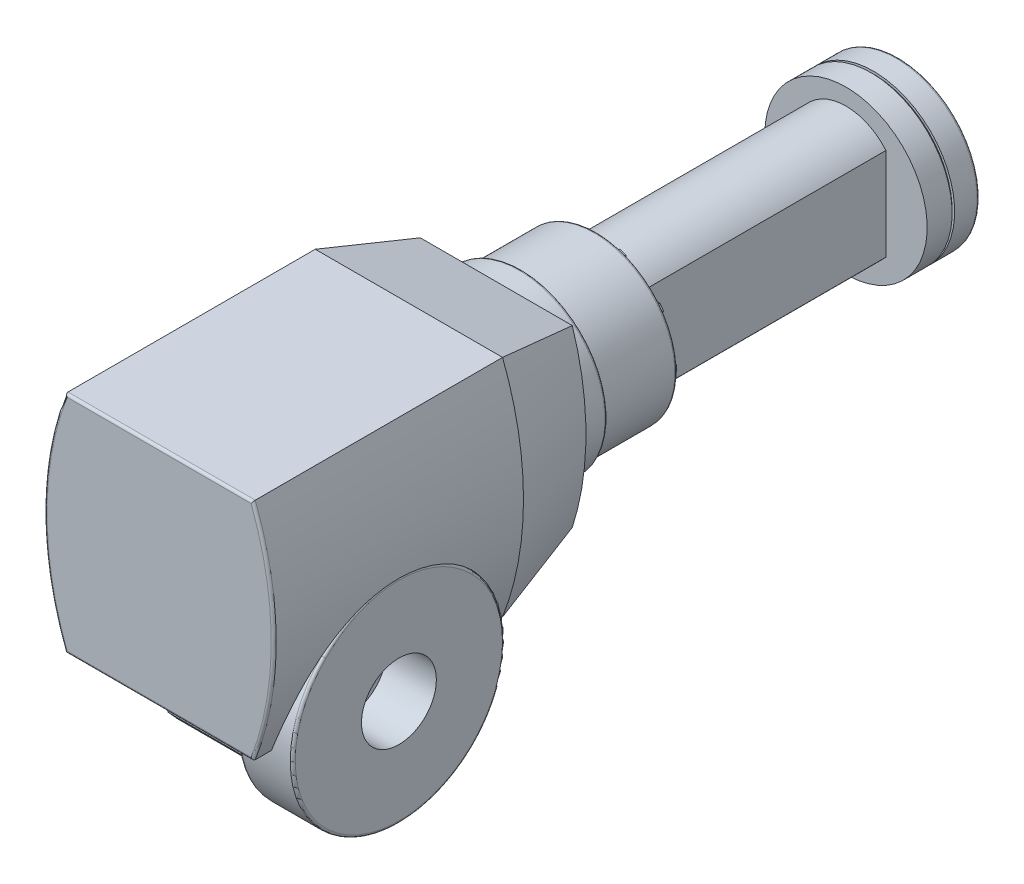
SolidWorks part; units mm, degrees
ref_plane "Front Plane" through (0, 0, 0) normal (0, 0, 1) x (1, 0, 0)
ref_plane "Top Plane" through (0, 0, 0) normal (0, 1, 0) x (1, 0, 0)
ref_plane "Right Plane" through (0, 0, 0) normal (1, 0, 0) x (0, 0, -1)
sketch "Sketch1" plane through (0, 0, 0) normal (0, 0, 1) x (1, 0, 0)
  line L0 (0, -45) -> (0, 45) construction
  line L2 (-37.5, -45) -> (37.5, -45)
  line L3 (-37.5, 45) -> (37.5, 45)
  arc A0 (-37.5, -45) -> (-37.5, 45) centre (79.119, 0) cw
  arc A1 (37.5, -45) -> (37.5, 45) centre (-79.119, 0) ccw
  point P4 (0, 0)
  point P8 (0, 0)
  point P11 (0, -45)
  point P14 (0, 45)
  dimension "D3" = 125
  dimension "D1" = 90
  dimension "D2" = 75
extrude "Boss-Extrude1" add sketch "Sketch1" along normal blind 100
sketch "Sketch2" plane through (0, 0, 0) normal (0, 0, -1) x (-1, 0, 0)
  line L2 (-37.5, -45) -> (37.5, -45)
  line L3 (37.5, 45) -> (-37.5, 45)
  line L4 (-37.5, -45) -> (37.5, -45)
  line L5 (37.5, 45) -> (-37.5, 45)
  arc A2 (-37.5, 45) -> (-37.5, -45) centre (79.119, 0) ccw
  arc A3 (37.5, -45) -> (37.5, 45) centre (-79.119, 0) ccw
  arc A4 (-37.5, 45) -> (-37.5, -45) centre (79.119, 0) ccw
  arc A5 (37.5, -45) -> (37.5, 45) centre (-79.119, 0) ccw
  dimension "D1" = 0
ref_plane "Plane1" through (0, 0, -35) normal (0, 0, -1) x (-1, 0, 0)
sketch "Sketch3" plane through (0, 0, -35) normal (0, 0, -1) x (-1, 0, 0)
  line L4 (-30.4255, -35) -> (30.4255, -35)
  line L5 (30.4255, 35) -> (-30.4255, 35)
  line L6 (-30.4255, -35) -> (30.4255, -35)
  line L7 (30.4255, 35) -> (-30.4255, 35)
  arc A4 (-30.4255, 35) -> (-30.4255, -35) centre (79.119, 0) ccw
  arc A5 (30.4255, -35) -> (30.4255, 35) centre (-79.119, 0) ccw
  arc A6 (-30.4255, 35) -> (-30.4255, -35) centre (79.119, 0) ccw
  arc A7 (30.4255, -35) -> (30.4255, 35) centre (-79.119, 0) ccw
  dimension "D1" = 10
loft "Loft1" add profiles "Sketch3", "Sketch2"
sketch "Sketch4" plane through (0, 0, -35) normal (0, 0, -1) x (-1, 0, 0)
  circle A0 centre (0, 0) radius 34.5
  dimension "D1" = 69
extrude "Boss-Extrude2" add sketch "Sketch4" along normal blind 10
sketch "Sketch5" plane through (0, 0, -45) normal (0, 0, -1) x (-1, 0, 0)
  circle A2 centre (0, 0) radius 32.5
  circle A3 centre (0, 0) radius 32.5
  dimension "D1" = 2
extrude "Boss-Extrude3" add sketch "Sketch5" along normal blind 30
sketch "Sketch6" plane through (0, 0, -75) normal (0, 0, -1) x (-1, 0, 0)
  line L0 (0, 0) -> (29, 0) construction
  line L1 (27.8349, 0.6726) -> (27.8349, -0.6726)
  line L2 (29, -2.5) -> (31.1651, -1.25)
  line L3 (31.1651, -1.25) -> (31.1651, 1.25)
  line L4 (31.1651, 1.25) -> (29, 2.5)
  line L5 (29, 2.5) -> (26.8349, 1.25)
  line L6 (26.8349, 1.25) -> (26.8349, -1.25)
  line L7 (26.8349, -1.25) -> (29, -2.5)
  line L8 (27.8349, -0.6726) -> (29, -1.3453)
  line L9 (29, -1.3453) -> (30.1651, -0.6726)
  line L10 (30.1651, -0.6726) -> (30.1651, 0.6726)
  line L11 (30.1651, 0.6726) -> (29, 1.3453)
  line L12 (29, 1.3453) -> (27.8349, 0.6726)
  circle A0 centre (29, 0) radius 2.1651 construction
  dimension "D1" = 29
  dimension "D2" = 5
  dimension "D3" = 1
extrude "Boss-Extrude4" add sketch "Sketch6" along normal blind 1
pattern_circular "CirPattern1" count 10 over 360 about axis through (0, 0, 0) along (0, 0, 1) of "Boss-Extrude4"
sketch "Sketch7" plane through (0, 0, -75) normal (0, 0, -1) x (-1, 0, 0)
  line L0 (0, -18.5) -> (0, 18.5) construction
  line L1 (0, 0) -> (16, 0) construction
  line L2 (16, -18.5) -> (16, 18.5)
  line L3 (-16, -18.5) -> (-16, 18.5)
  arc A0 (-16, 18.5) -> (16, 18.5) centre (0, 4.8985) cw
  arc A1 (-16, -18.5) -> (16, -18.5) centre (0, -4.8985) ccw
  point P4 (0, 0)
  point P10 (16, 0)
  dimension "D3" = 21
  dimension "D1" = 37
  dimension "D2" = 16
extrude "Boss-Extrude5" add sketch "Sketch7" along normal blind 100
sketch "Sketch8" plane through (0, 0, -175) normal (0, 0, -1) x (-1, 0, 0)
  circle A0 centre (0, 0) radius 32.5 construction
  circle A1 centre (0, 0) radius 32.5
extrude "Boss-Extrude6" add sketch "Sketch8" along normal blind 10
sketch "Sketch9" plane through (0, 0, -185) normal (0, 0, -1) x (-1, 0, 0)
  circle A2 centre (0, 0) radius 31.5
  circle A3 centre (0, 0) radius 31.5
  dimension "D1" = 1
extrude "Boss-Extrude7" add sketch "Sketch9" along normal blind 1
sketch "Sketch10" plane through (0, 0, -186) normal (0, 0, -1) x (-1, 0, 0)
  circle A0 centre (0, 0) radius 32.5 construction
  circle A3 centre (0, 0) radius 32.5
extrude "Boss-Extrude8" add sketch "Sketch10" along normal blind 10 separate body
sketch "Sketch11" plane through (0, 0, -186) normal (0, 0, -1) x (-1, 0, 0)
  circle A1 centre (0, 0) radius 31.5
  circle A2 centre (0, 0) radius 31.5
  dimension "D1" = 0
ref_plane "Plane2" through (35, 0, 0) normal (1, 0, 0) x (0, 0, -1)
sketch "Sketch13" plane through (35, 0, 0) normal (1, 0, 0) x (0, 0, -1)
  line L0 (-100, -45) -> (0, -45) construction
  circle A0 centre (-50, -45) radius 42.5
  dimension "D1" = 85
extrude "Boss-Extrude9" add sketch "Sketch13" along normal mid plane 22 separate body
sketch "Sketch14" plane through (24, 0, 0) normal (-1, 0, 0) x (0, 0, 1)
  line L0 (50, -45) -> (50, -75) construction
  line L1 (100, -45) -> (0, -45) construction
  line L2 (30, -45) -> (30, -75)
  line L3 (70, -45) -> (70, -75)
  line L4 (30, -45) -> (70, -45)
  arc A0 (30, -75) -> (70, -75) centre (50, -60.3358) ccw
  dimension "D4" = 24.8
  dimension "D1" = 30
  dimension "D2" = 20
  dimension "D3" = 20
extrude "Boss-Extrude10" add sketch "Sketch14" along normal blind 35
ref_plane "Plane3" through (0, 0, 50) normal (0, 0, 1) x (1, 0, 0)
sketch "Sketch15" plane through (0, 0, 50) normal (0, 0, 1) x (1, 0, 0)
  line L0 (-11, -45) -> (-11, -90)
  line L1 (-11, -45) -> (-36, -45)
  line L2 (-37.5, -45) -> (37.5, -45) construction
  arc A0 (-36, -45) -> (-11, -90) centre (18.9889, -43.8951) ccw
  dimension "D3" = 55
  dimension "D1" = 25
  dimension "D2" = 45
extrude "Boss-Extrude11" add sketch "Sketch15" against normal mid plane 40
sketch "Sketch16" plane through (-11, 0, 0) normal (1, 0, 0) x (0, 0, -1)
  line L3 (-70, -75) -> (-70, -90)
  line L4 (-70, -90) -> (-30, -90)
  line L5 (-30, -90) -> (-30, -75)
  line L6 (-70, -75) -> (-70, -90)
  line L7 (-70, -90) -> (-30, -90)
  line L8 (-30, -90) -> (-30, -75)
  arc A1 (-70, -75) -> (-30, -75) centre (-50, -60.3358) ccw
  arc A2 (-70, -75) -> (-30, -75) centre (-50, -60.3358) ccw
  dimension "D1" = 0
extrude "Cut-Extrude1" cut sketch "Sketch16" against normal blind 40
fillet "Fillet1" radius 1 8 edges at (0, -45, 100) (-45.881, 0, 100) (0, 45, 100) (45.881, 0, 100) (-34.5, 0, -45) (-32.5, 0, -75) (46, -45, 7.5) (24, -87.5, 50)
fillet "Fillet2" radius 1 1 edges at (-32.5, 0, -196)
sketch "Sketch17" plane through (0, 0, -196) normal (0, 0, -1) x (-1, 0, 0)
  circle A0 centre (0, 0) radius 15
  dimension "D1" = 30
extrude "Cut-Extrude2" cut sketch "Sketch17" against normal blind 20
sketch "Sketch18" plane through (46, 0, 0) normal (1, 0, 0) x (0, 0, -1)
  circle A1 centre (-50, -45) radius 15
  dimension "D1" = 30
extrude "Cut-Extrude3" cut sketch "Sketch18" against normal blind 20
